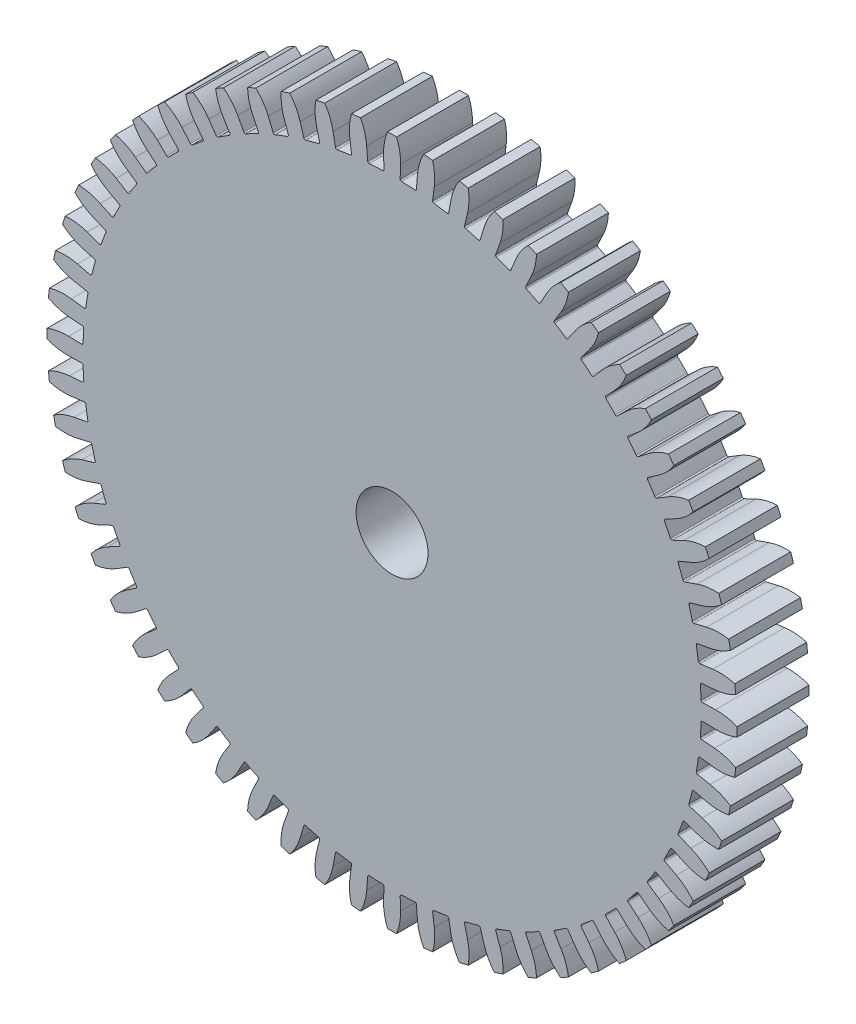
SolidWorks part; units mm, degrees
ref_plane "Front Plane" through (0, 0, 0) normal (0, 0, 1) x (1, 0, 0)
ref_plane "Top Plane" through (0, 0, 0) normal (0, 1, 0) x (1, 0, 0)
ref_plane "Right Plane" through (0, 0, 0) normal (1, 0, 0) x (0, 0, -1)
sketch "Sketch1" plane through (0, 0, 0) normal (0, 0, 1) x (1, 0, 0)
  line L0 (0, 0) -> (6.94, 0) construction
  line L1 (0, 0) -> (4.2941, 0.225) construction
  line L2 (0, 0) -> (5.3526, 0.1402) construction
  line L3 (0, 0) -> (5.9482, 0.0779) construction
  line L4 (4.2985, 0.1126) -> (4.4985, 0.1178)
  line L5 (0, 0) -> (4.2941, 0.225)
  line L6 (4.2985, -0.1126) -> (4.4985, -0.1178)
  line L7 (0, 0) -> (4.2941, -0.225) construction
  line L8 (0, 0) -> (4.2941, -0.225)
  arc A0 (4.8, 0) -> (4.7984, 0.1256) centre (0, 0) ccw construction
  circle A1 centre (0, 0) radius 4.5 construction
  arc A2 (4.2985, 0.1126) -> (4.3, 0) centre (0, 0) ccw construction
  arc A3 (4.4985, 0.1178) -> (4.7996, 0.0628) centre (4.518, -0.6276) cw
  arc A4 (4.7996, 0.0628) -> (4.7996, -0.0628) centre (0, 0) cw
  arc A5 (4.2941, 0.225) -> (4.2985, 0.1126) centre (0, 0) cw
  arc A6 (4.4985, -0.1178) -> (4.7996, -0.0628) centre (4.518, 0.6276) ccw
  arc A7 (4.2941, -0.225) -> (4.2985, -0.1126) centre (0, 0) ccw
  dimension "D1" = 9.6
  dimension "D2" = 9
  dimension "D3" = 0.5
  dimension "D4" = 3
  dimension "D5" = 1.5
  dimension "D6" = 0.75
extrude "Boss-Extrude1" add sketch "Sketch1" along normal blind 1 contours L8 A7 L6 A6 A4 A3 L4 A5 L5 region at (3.0311, 0, 0)
fillet "Fillet1" radius 0.02 2 edges at (4.2985, -0.1126, 0.5) (4.2985, 0.1126, 0.5)
pattern_circular "CirPattern1" count 60 over 360 about axis through (0, 0, 1) along (0, 0, -1) of "Fillet1", "Boss-Extrude1"
ref_plane "Plane1" through (4.2606, -0.581, 1) normal (0.1351, 0.9908, 0) x (0.9908, -0.1351, 0)
sketch "Sketch4" plane through (0, 0, 1) normal (0, 0, 1) x (1, 0, 0)
  circle A0 centre (0, 0) radius 0.5
extrude "Cut-Extrude2" cut sketch "Sketch4" against normal blind 1
